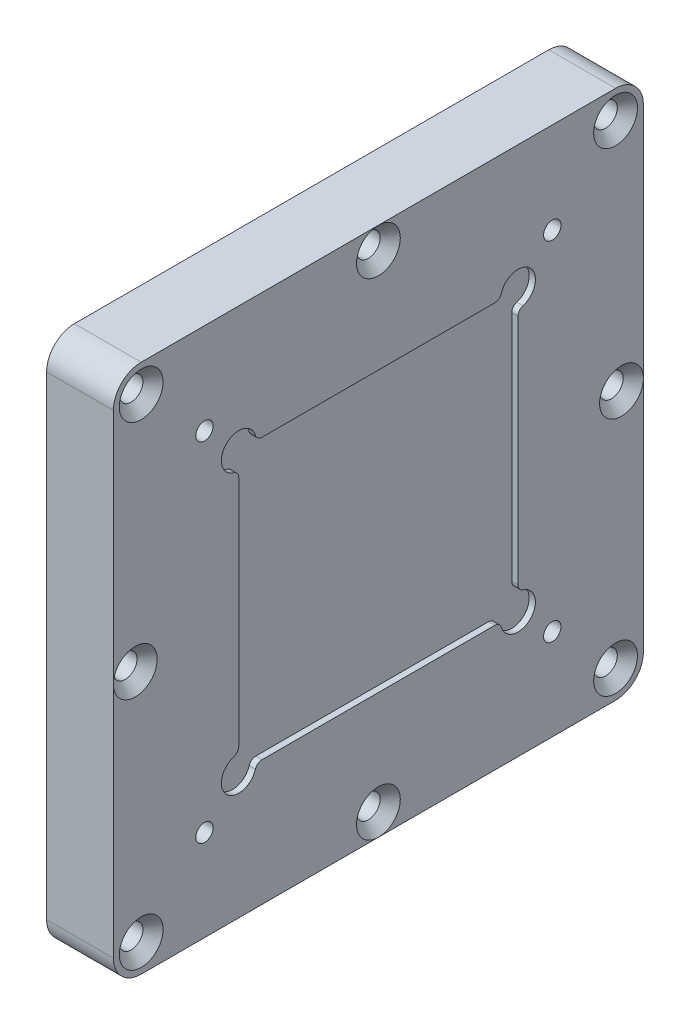
SolidWorks part; units mm, degrees
ref_plane "Front Plane" through (0, 0, 0) normal (0, 0, 1) x (1, 0, 0)
ref_plane "Top Plane" through (0, 0, 0) normal (0, 1, 0) x (1, 0, 0)
ref_plane "Right Plane" through (0, 0, 0) normal (1, 0, 0) x (0, 0, -1)
sketch "Sketch2" plane through (0, 0, 0) normal (1, 0, 0) x (0, 0, -1)
  line L1 (-34.1, -38.1) -> (34.1, -38.1)
  line L2 (-38.1, -34.1) -> (-38.1, 34.1)
  line L3 (-34.1, 38.1) -> (34.1, 38.1)
  line L4 (38.1, -34.1) -> (38.1, 34.1)
  line L5 (-38.1, -38.1) -> (38.1, 38.1) construction
  line L6 (-38.1, 38.1) -> (38.1, -38.1) construction
  arc A0 (-34.1, -38.1) -> (-38.1, -34.1) centre (-34.1, -34.1) cw
  arc A1 (34.1, -38.1) -> (38.1, -34.1) centre (34.1, -34.1) ccw
  arc A2 (34.1, 38.1) -> (38.1, 34.1) centre (34.1, 34.1) cw
  arc A3 (-38.1, 34.1) -> (-34.1, 38.1) centre (-34.1, 34.1) cw
  point P0 (0, 0)
  dimension "D3" = 4
  dimension "D1" = 76.2
  dimension "D2" = 76.2
extrude "Boss-Extrude1" add sketch "Sketch2" along normal blind 9.6
sketch "Sketch21" plane through (9.6, 0, 0) normal (-1, 0, 0) x (0, 0, 1)
  line L0 (-34.1, 34.1) -> (-34.1, -34.1) construction
  line L1 (-34.1, -34.1) -> (34.1, -34.1) construction
  line L2 (-38.1, -34.1) -> (-38.1, 34.1) construction
  line L3 (-34.1, 38.1) -> (34.1, 38.1) construction
  line L4 (38.1, 34.1) -> (38.1, -34.1) construction
  line L5 (34.1, -38.1) -> (-34.1, -38.1) construction
  line L6 (34.1, -34.1) -> (34.1, 34.1) construction
  line L7 (34.1, 34.1) -> (-34.1, 34.1) construction
  dimension "D1" = 4
  dimension "D2" = 4
  dimension "D3" = 4
  dimension "D4" = 4
sketch "Sketch22" plane through (9.6, 0, 0) normal (-1, 0, 0) x (0, 0, 1)
  line L0 (38.1, 34.1) -> (38.1, -34.1) construction
  line L1 (-38.1, -34.1) -> (-38.1, 34.1) construction
  line L3 (34.1, -38.1) -> (-34.1, -38.1) construction
  line L4 (-34.1, 38.1) -> (34.1, 38.1) construction
  point P0 (-34.1, 34.1)
  point P3 (34.1, 34.1)
  point P6 (34.1, -34.1)
  point P9 (-34.1, -34.1)
  point P12 (0, 34.95)
  point P14 (34.95, 0)
  point P16 (0, -34.95)
  point P18 (-34.95, 0)
  dimension "D1" = 3.15
  dimension "D2" = 3.15
  dimension "D3" = 3.15
  dimension "D4" = 3.15
sketch "Sketch24" plane through (9.6, 0, 0) normal (1, 0, 0) x (0, 0, -1)
  line L1 (20.075, -20.075) -> (-20.075, -20.075)
  line L2 (20.075, -20.075) -> (20.075, 20.075)
  line L3 (20.075, 20.075) -> (-20.075, 20.075)
  line L4 (-20.075, -20.075) -> (-20.075, 20.075)
  line L5 (20.075, -20.075) -> (-20.075, 20.075) construction
  line L6 (20.075, 20.075) -> (-20.075, -20.075) construction
  circle A0 centre (-20.075, 20.075) radius 2.5
  circle A1 centre (20.075, 20.075) radius 2.5
  circle A2 centre (20.075, -20.075) radius 2.5
  circle A3 centre (-20.075, -20.075) radius 2.5
  point P0 (0, 0)
  dimension "D3" = 5
  dimension "D4" = 5
  dimension "D5" = 5
  dimension "D6" = 5
  dimension "D1" = 40.15
  dimension "D2" = 40.15
extrude "Cut-Extrude1" cut sketch "Sketch24" against normal blind 0.9 contours A3 L1 A2 L2 A1 L3 A0 L4 | L3 A0 L4 | L4 A0 L3 | L3 A1 L2 | L2 A1 L3 | L1 A2 L2 | L2 A2 L1 | L4 A3 L1 | L1 L4 L3 L2 region at (9.6, -20.4287, 20.4287) region at (9.6, 0, 0) region at (9.6, -19.014, -19.014) region at (9.6, -20.4287, -20.4287) region at (9.6, 20.4287, 20.4287) region at (9.6, 19.014, 19.014) region at (9.6, 19.014, -19.014) region at (9.6, 20.4287, -20.4287)
fillet "Fillet1" radius 1 8 edges at (9.15, -20.075, 17.575) (9.15, -17.575, 20.075) (9.15, -17.575, -20.075) (9.15, -20.075, -17.575) (9.15, 17.575, -20.075) (9.15, 20.075, -17.575) (9.15, 20.075, 17.575) (9.15, 17.575, 20.075)
sketch "Sketch27" plane through (9.6, 0, 0) normal (1, 0, 0) x (0, 0, -1)
  line L0 (-25, 25) -> (25, -25) construction
  line L2 (-25, -25) -> (25, 25) construction
  point P0 (-25, 25)
  point P2 (25, 25)
  point P4 (25, -25)
  point P6 (-25, -25)
  point P21 (0, 0)
  dimension "D1" = 50
  dimension "D2" = 50
sketch "Sketch31" plane through (0, 0, 0) normal (-1, 0, 0) x (0, 0, 1)
  point P0 (-16, 16)
  point P2 (16, 16)
  point P4 (16, -16)
  point P6 (-16, -16)
  point P9 (0, 0)
  point P10 (0, 0)
  point P11 (0, 0)
  point P12 (-16.0947, -12.9001)
  point P14 (15.7045, -16)
  point P15 (16, -16)
  dimension "D1" = 32
  dimension "D2" = 32
  dimension "D3" = 16
  dimension "D4" = 16
sketch "Sketch33" plane through (0, 0, 0) normal (-1, 0, 0) x (0, 0, 1)
  line L0 (-36.9284, 36.9284) -> (36.9284, -36.9284) construction
  circle A0 centre (0, 0) radius 5
  arc A1 (34.1, -38.1) -> (38.1, -34.1) centre (34.1, -34.1) ccw construction
  arc A2 (-34.1, 38.1) -> (-38.1, 34.1) centre (-34.1, 34.1) ccw construction
  point P3 (-3.5355, 3.5355)
  point P4 (3.5355, -3.5355)
  point P5 (-3.5355, -3.5355)
  point P6 (3.5355, 3.5355)
  point P7 (0, 0)
  point P8 (36.9284, -36.9284)
  point P16 (-36.9284, 36.9284)
  dimension "D1" = 10
curve "Helix/Spiral1" [suppressed]
sketch "Sketch36" plane through (0, 0, 0) normal (0, 0, 1) x (1, 0, 0)
  line L1 (-6, -1.75) -> (6, -1.75)
  line L2 (-6, -1.75) -> (-6, 1.75)
  line L3 (-6, 1.75) -> (6, 1.75)
  line L4 (6, -1.75) -> (6, 1.75)
  line L5 (-6, -1.75) -> (6, 1.75) construction
  line L6 (-6, 1.75) -> (6, -1.75) construction
  point P0 (0, 0)
  dimension "D1" = 12
  dimension "D2" = 3.5
sweep "Cut-Sweep1" [suppressed] cut profiles "Sketch36" path "Helix/Spiral1"
ref_axis "Axis1" [suppressed] through (10.08, 0, 0) along (-1, 0, 0)
pattern_circular "CirPattern1" [suppressed] count 14 every 30 about axis through (10.08, 0, 0) along (-1, 0, 0) of bodies 119
hole_wizard "CSK for M3 Flat Head Machine Screw1" positions "Sketch22" profile "Sketch23" countersink size "M3" standard "ANSI Metric" end condition through all
sketch "Sketch23" plane through (9.6, 34.1, -34.1) normal (0, 1, 0) x (0, 0, -1)
  line L0 (0, 0) -> (0, 9.6)
  line L1 (0, 9.6) -> (1.7, 9.6)
  line L2 (1.7, 9.6) -> (1.7, 1.45)
  line L3 (1.7, 1.45) -> (3.15, 0)
  line L5 (3.15, 0) -> (0, 0)
  line L6 (-1.7, 1.45) -> (-3.15, 0) construction
  line L11 (0, -6.35) -> (0, 107.95) construction
  dimension "Thru Hole Dia." = 3.4
  dimension "Thru Hole Depth" = 9.6
  dimension "Near C'Sink Dia." = 6.3
  dimension "Near C'Sink Angle" = 90
hole_wizard "M3x0.5 Tapped Hole1" positions "Sketch27" profile "Sketch26" tap size "M3x0.5" standard "ANSI Metric"
sketch "Sketch26" plane through (9.6, 25, 25) normal (0, 1, 0) x (0, 0, -1)
  line L0 (0, 0) -> (0, 8.3711)
  line L1 (0, 8.3711) -> (1.25, 7.62)
  line L2 (1.25, 7.62) -> (1.25, 0)
  line L5 (1.25, 0) -> (0, 0)
  line L10 (0, 8.3711) -> (-1.25, 7.62) construction
  line L11 (0, -6.35) -> (0, 107.95) construction
  dimension "Tap Drill Dia." = 2.5
  dimension "Tap Drill Depth" = 7.62
  dimension "Drill Angle" = 118
hole_wizard "M3x0.5 Tapped Hole2" positions "Sketch31" profile "Sketch30" tap size "M3x0.5" standard "ANSI Metric"
sketch "Sketch30" plane through (0, 16, -16) normal (0, 1, 0) x (0, 0, 1)
  line L0 (0, 0) -> (0, 5.8311)
  line L1 (0, 5.8311) -> (1.25, 5.08)
  line L2 (1.25, 5.08) -> (1.25, 0)
  line L5 (1.25, 0) -> (0, 0)
  line L10 (0, 5.8311) -> (-1.25, 5.08) construction
  line L11 (0, -6.35) -> (0, 107.95) construction
  dimension "Tap Drill Dia." = 2.5
  dimension "Tap Drill Depth" = 5.08
  dimension "Drill Angle" = 118
sketch "Sketch37" plane through (0, 0, 0) normal (-1, 0, 0) x (0, 0, 1)
  line L0 (-1.75, 1.75) -> (-1.75, 25.4)
  line L1 (-1.75, 1.75) -> (-25.4, 1.75)
  line L2 (-1.75, -1.75) -> (-25.4, -1.75)
  line L3 (-1.75, -1.75) -> (-1.75, -25.4)
  line L4 (1.75, -25.4) -> (1.75, -1.75)
  line L5 (1.75, -1.75) -> (25.4, -1.75)
  line L6 (1.75, 25.4) -> (1.75, 1.75)
  line L7 (1.75, 1.75) -> (25.4, 1.75)
  line L8 (34.1, -38.1) -> (-34.1, -38.1) construction
  line L9 (-2.75, -2.75) -> (-2.75, -25.4)
  line L10 (-2.75, -2.75) -> (-25.4, -2.75)
  line L11 (-2.75, 2.75) -> (-2.75, 25.4)
  line L12 (-2.75, 2.75) -> (-25.4, 2.75)
  line L13 (2.75, 25.4) -> (2.75, 2.75)
  line L14 (2.75, 2.75) -> (25.4, 2.75)
  line L15 (2.75, -25.4) -> (2.75, -2.75)
  line L16 (2.75, -2.75) -> (25.4, -2.75)
  line L17 (-6.75, -6.75) -> (-6.75, -25.4)
  line L18 (-6.75, -6.75) -> (-25.4, -6.75)
  line L19 (-11.75, 11.75) -> (-25.4, 11.75)
  line L20 (-11.75, 11.75) -> (-11.75, 25.4)
  line L21 (11.75, 25.4) -> (11.75, 11.75)
  line L22 (11.75, 11.75) -> (25.4, 11.75)
  line L23 (-6.75, 6.75) -> (-6.75, 25.4)
  line L24 (-6.75, 6.75) -> (-25.4, 6.75)
  line L25 (6.75, 25.4) -> (6.75, 6.75)
  line L26 (6.75, 6.75) -> (25.4, 6.75)
  line L27 (34.1, -34.1) -> (34.1, 34.1)
  line L28 (34.1, 34.1) -> (-34.1, 34.1)
  line L29 (-34.1, 34.1) -> (-34.1, -34.1)
  line L30 (-34.1, -34.1) -> (34.1, -34.1)
  line L31 (34.1, -34.1) -> (34.1, 34.1)
  line L32 (34.1, 34.1) -> (-34.1, 34.1)
  line L33 (-34.1, 34.1) -> (-34.1, -34.1)
  line L34 (-34.1, -34.1) -> (34.1, -34.1)
  line L35 (6.75, -25.4) -> (6.75, -6.75)
  line L36 (6.75, -6.75) -> (25.4, -6.75)
  line L37 (-7.75, -7.75) -> (-7.75, -25.4)
  line L38 (-7.75, -7.75) -> (-25.4, -7.75)
  line L39 (-7.75, 7.75) -> (-7.75, 25.4)
  line L40 (-7.75, 7.75) -> (-25.4, 7.75)
  line L41 (7.75, 25.4) -> (7.75, 7.75)
  line L42 (7.75, 7.75) -> (25.4, 7.75)
  line L43 (7.75, -25.4) -> (7.75, -7.75)
  line L44 (7.75, -7.75) -> (25.4, -7.75)
  line L45 (-11.75, -11.75) -> (-11.75, -25.4)
  line L46 (-11.75, -11.75) -> (-25.4, -11.75)
  line L47 (-25.4, 12.75) -> (-19.75, 12.75)
  line L48 (25.4, -25.4) -> (-25.4, -25.4)
  line L49 (25.4, -25.4) -> (25.4, 25.4)
  line L50 (25.4, 25.4) -> (-25.4, 25.4)
  line L51 (-25.4, -25.4) -> (-25.4, 25.4)
  line L52 (25.4, -25.4) -> (-25.4, 25.4) construction
  line L53 (25.4, 25.4) -> (-25.4, -25.4) construction
  line L54 (-19.75, 12.75) -> (-19.75, 19.75)
  line L55 (-19.75, 19.75) -> (-12.75, 19.75)
  line L56 (-12.75, 19.75) -> (-12.75, 25.4)
  line L57 (12.75, 25.4) -> (12.75, 19.75)
  line L58 (12.75, 19.75) -> (19.75, 19.75)
  line L59 (19.75, 19.75) -> (19.75, 12.75)
  line L60 (19.75, 12.75) -> (25.4, 12.75)
  line L61 (-25.4, -12.75) -> (-19.75, -12.75)
  line L62 (-19.75, -12.75) -> (-19.75, -19.75)
  line L63 (-19.75, -19.75) -> (-12.75, -19.75)
  line L64 (-12.75, -19.75) -> (-12.75, -25.4)
  line L65 (12.75, -25.4) -> (12.75, -19.75)
  line L66 (12.75, -19.75) -> (19.75, -19.75)
  line L67 (19.75, -19.75) -> (19.75, -12.75)
  line L68 (19.75, -12.75) -> (25.4, -12.75)
  line L69 (11.75, -25.4) -> (11.75, -11.75)
  line L70 (11.75, -11.75) -> (25.4, -11.75)
  line L71 (-20.4503, -25.4) -> (-25.4, -20.4503)
  line L72 (-25.4, 20.4503) -> (-20.4503, 25.4)
  line L73 (20.4503, 25.4) -> (25.4, 20.4503)
  line L74 (20.4503, -25.4) -> (25.4, -20.4503)
  point P0 (0, 0)
  point P100 (21.4595, 25.4)
  dimension "D1" = 1.75
  dimension "D2" = 1.75
  dimension "D3" = 1.75
  dimension "D4" = 1.75
  dimension "D9" = 23.65
  dimension "D23" = 1
  dimension "D24" = 7
  dimension "D25" = 7
  dimension "D5" = 1
  dimension "D6" = 1
  dimension "D7" = 1
  dimension "D8" = 1
  dimension "D10" = 4
  dimension "D11" = 4
  dimension "D12" = 4
  dimension "D13" = 4
  dimension "D14" = 4
  dimension "D15" = 1
  dimension "D16" = 1
  dimension "D17" = 1
  dimension "D18" = 1
  dimension "D19" = 4
  dimension "D20" = 4
  dimension "D21" = 4
  dimension "D22" = 4
extrude "Cut-Extrude2" cut sketch "Sketch37" against normal blind 6 contours L72 L51 L47 L54 L55 L56 L50 | L71 L48 L64 L63 L62 L61 L51 | L48 L74 L49 L68 L67 L66 L65 | L73 L50 L57 L58 L59 L60 L49 | L21 L50 L41 L42 L49 L22 | L25 L50 L13 L14 L49 L26 | L51 L2 L3 L48 L4 L5 L49 L7 L6 L50 L0 L1 | L51 L12 L11 L50 L23 L24 | L51 L40 L39 L50 L20 L19 | L51 L18 L17 L48 L9 L10 | L51 L46 L45 L48 L37 L38 | L36 L49 L16 L15 L48 L35 | L69 L70 L49 L44 L43 L48 region at (0, 0, 0) region at (0, 14.075, -3.0703) region at (0, 25.0797, 4.75) region at (0, -3.0703, -14.075) region at (0, 16.575, -7.9996) region at (0, 25.1504, 9.75) region at (0, -7.9996, -16.575) region at (0, -4.75, 25.0797) region at (0, 19.8966, -19.8966) region at (0, 19.8966, 19.8966) region at (0, -19.8966, -19.8966) region at (0, -9.75, 25.1504) region at (0, -19.8966, 19.8966)
chamfer "Chamfer1" distance 4 angle 45 20 edges at (6, 9.75, -25.4) (6, 4.75, -25.4) (6, 0, -25.4) (6, -4.75, -25.4) (6, -9.75, -25.4) (6, -25.4, -9.75) (6, -25.4, -4.75) (6, -25.4, 0) (6, -25.4, 4.75) (6, -25.4, 9.75) (6, -9.75, 25.4) (6, -4.75, 25.4) (6, 0, 25.4) (6, 4.75, 25.4) (6, 9.75, 25.4) (6, 25.4, 9.75) (6, 25.4, 4.75) (6, 25.4, 0) (6, 25.4, -4.75) (6, 25.4, -9.75)
fillet "Fillet2" radius 1.6 126 edges at (1, 25.4, -7.75) (4, 23.4, -7.75) (4, 23.4, -2.75) (1, 25.4, -2.75) (1, 25.4, 1.75) (4, 23.4, 1.75) (4, 23.4, 6.75) (1, 25.4, 6.75) (1, 25.4, 11.75) (4, 23.4, 11.75) (4, 23.4, 7.75) (1, 25.4, 7.75) (4, 23.4, 2.75) (1, 25.4, 2.75) (4, 23.4, -1.75) (1, 25.4, -1.75) (4, 23.4, -6.75) (1, 25.4, -6.75) (4, 23.4, -11.75) (1, 25.4, -11.75) (3, 20.4503, 25.4) (3, 25.4, 20.4503) (3, 25.4, 12.75) (3, 19.75, 12.75) (3, -19.75, -12.75) (3, -12.75, 19.75) (3, -19.75, 12.75) (3, -25.4, 12.75) (3, -25.4, 20.4503) (3, -20.4503, 25.4) (3, -12.75, 25.4) (4, -6.75, 23.4) (1, -6.75, 25.4) (4, -1.75, 23.4) (1, -1.75, 25.4) (4, 2.75, 23.4) (1, 2.75, 25.4) (4, 7.75, 23.4) (1, 7.75, 25.4) (3, 12.75, 25.4) (4, 11.75, 23.4) (1, 11.75, 25.4) (4, 6.75, 23.4) (1, 6.75, 25.4) (4, 1.75, 23.4) (1, 1.75, 25.4) (4, -2.75, 23.4) (1, -2.75, 25.4) (4, -7.75, 23.4) (1, -7.75, 25.4) (4, -11.75, 23.4) (1, -11.75, 25.4) (1, -25.4, 11.75) (4, -23.4, 11.75) (1, -25.4, 7.75) (4, -23.4, 7.75) (1, -25.4, 6.75) (4, -23.4, 6.75) (1, -25.4, 2.75) (4, -23.4, 2.75) (3, -25.4, -12.75) (3, -25.4, -20.4503) (3, -20.4503, -25.4) (3, -12.75, -25.4) (3, -12.75, -19.75) (3, 12.75, -19.75) (3, 19.75, -12.75) (3, 25.4, -12.75) (3, 25.4, -20.4503) (3, 20.4503, -25.4) (3, 12.75, -25.4) (4, 7.75, -23.4) (1, 7.75, -25.4) (4, 2.75, -23.4) (1, 2.75, -25.4) (1, -1.75, -25.4) (4, -1.75, -23.4) (4, -7.75, -23.4) (4, -2.75, -23.4) (4, 1.75, -23.4) (4, 6.75, -23.4) (4, 11.75, -23.4) (1, 11.75, -25.4) (1, 6.75, -25.4) (1, 1.75, -25.4) (1, -2.75, -25.4) (1, -7.75, -25.4) (1, -11.75, -25.4) (4, -11.75, -23.4) (4, -23.4, -7.75) (4, -23.4, -11.75) (4, -23.4, -6.75) (4, -23.4, -2.75) (4, -23.4, 1.75) (4, -23.4, -1.75) (1, -25.4, -1.75) (1, -25.4, 1.75) (1, -25.4, -2.75) (1, -25.4, -6.75) (1, -25.4, -7.75) (1, -25.4, -11.75) (3, -19.75, -19.75) (3, -11.75, -11.75) (3, -6.75, -6.75) (3, -7.75, -7.75) (3, -2.75, -2.75) (3, 19.75, -19.75) (3, 11.75, -11.75) (3, 7.75, -7.75) (3, 2.75, -2.75) (3, 1.75, 1.75) (3, 6.75, 6.75) (3, 11.75, 11.75) (3, 19.75, 19.75) (3, 7.75, 7.75) (3, 2.75, 2.75) (3, 1.75, -1.75) (3, -1.75, -1.75) (3, -19.75, 19.75) (3, -11.75, 11.75) (3, -7.75, 7.75) (3, -6.75, 6.75) (3, -1.75, 1.75) (3, -2.75, 2.75) (4, -6.75, -23.4) (1, -6.75, -25.4)
